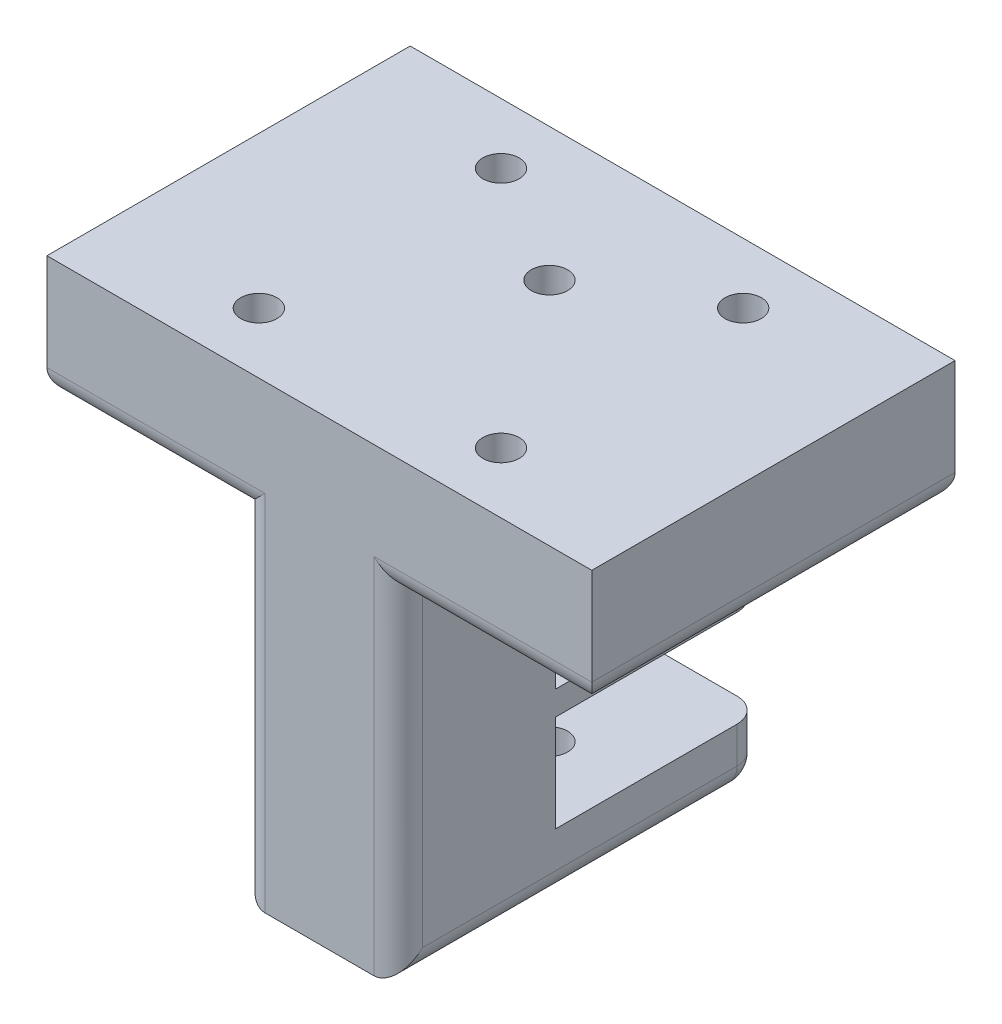
SolidWorks part; units mm, degrees
ref_plane "Front Plane" through (0, 0, 0) normal (0, 0, 1) x (1, 0, 0)
ref_plane "Top Plane" through (0, 0, 0) normal (0, 1, 0) x (1, 0, 0)
ref_plane "Right Plane" through (0, 0, 0) normal (1, 0, 0) x (0, 0, -1)
sketch "Sketch1" plane through (0, 0, 0) normal (0, 1, 0) x (1, 0, 0)
  line L1 (-20.4957, 14.8137) -> (24.5043, 14.8137)
  line L2 (-20.4957, 14.8137) -> (-20.4957, -15.1863)
  line L3 (-20.4957, -15.1863) -> (24.5043, -15.1863)
  line L4 (24.5043, 14.8137) -> (24.5043, -15.1863)
  line L5 (-20.4957, 14.8137) -> (24.5043, -15.1863) construction
  line L6 (-20.4957, -15.1863) -> (24.5043, 14.8137) construction
  line L11 (-7.9957, 9.8137) -> (12.0043, 9.8137) construction
  line L12 (-7.9957, 9.8137) -> (-7.9957, -10.1863) construction
  line L13 (-7.9957, -10.1863) -> (12.0043, -10.1863) construction
  line L14 (12.0043, 9.8137) -> (12.0043, -10.1863) construction
  line L15 (-7.9957, 9.8137) -> (12.0043, -10.1863) construction
  line L16 (-7.9957, -10.1863) -> (12.0043, 9.8137) construction
  circle A0 centre (-7.9957, 9.8137) radius 1.5
  circle A1 centre (12.0043, 9.8137) radius 1.5
  circle A2 centre (12.0043, -10.1863) radius 1.5
  circle A3 centre (-7.9957, -10.1863) radius 1.5
  point P0 (2.0043, -0.1863)
  point P7 (12.0043, 9.8137)
  point P9 (12.2604, -8.796)
  point P17 (0, 0)
  point P18 (0, 0)
  point P19 (0, 0)
  point P20 (0, 0)
  point P21 (0, 0)
  point P22 (-9.0809, -8.1131)
  dimension "D1" = 3
  dimension "D2" = 45
  dimension "D3" = 30
  dimension "D4" = 20
  dimension "D5" = 20
extrude "Boss-Extrude1" add sketch "Sketch1" against normal blind 10 contours L4 L1 L2 L3 A3 A2 A1 A0 region at (2.0043, 0, 0.1863)
sketch "Sketch5" plane through (0, -10, 0) normal (0, -1, 0) x (1, 0, 0)
  line L0 (-20.4957, 15.1863) -> (24.5043, 15.1863) construction
  line L1 (-4.4957, 15.1863) -> (8.5043, 15.1863)
  line L2 (-4.4957, 15.1863) -> (-4.4957, -14.8137)
  line L3 (-4.4957, -14.8137) -> (8.5043, -14.8137)
  line L4 (8.5043, 15.1863) -> (8.5043, -14.8137)
  line L5 (-20.4957, -14.8137) -> (24.5043, -14.8137) construction
  line L6 (-20.4957, -14.8137) -> (-20.4957, 15.1863) construction
  line L7 (-20.4957, 15.1863) -> (24.5043, 15.1863) construction
  line L8 (-20.4957, 15.1863) -> (-20.4957, -14.8137) construction
  line L9 (-20.4957, -14.8137) -> (24.5043, -14.8137) construction
  line L10 (24.5043, 15.1863) -> (24.5043, -14.8137) construction
  line L11 (-20.4957, 15.1863) -> (24.5043, -14.8137) construction
  line L12 (-20.4957, -14.8137) -> (24.5043, 15.1863) construction
  line L13 (2.0043, -999.8137) -> (2.0043, 49000.1863) construction
  point P8 (2.0043, 0.1863)
  dimension "D1" = 13
extrude "Boss-Extrude2" add sketch "Sketch5" along normal blind 28
sketch "Sketch6" plane through (0, -38, 0) normal (0, -1, 0) x (1, 0, 0)
  line L0 (8.5043, -14.8137) -> (8.5043, 15.1863) construction
  line L1 (-4.4957, 15.1863) -> (8.5043, 15.1863)
  line L2 (-4.4957, 15.1863) -> (-4.4957, 5.1863)
  line L3 (-4.4957, 5.1863) -> (8.5043, 5.1863)
  line L4 (8.5043, 15.1863) -> (8.5043, 5.1863)
  line L5 (2.0043, 5.1863) -> (2.0043, 15.1863) construction
  line L6 (-4.4957, 10.1863) -> (8.5043, 10.1863) construction
  point P232 (2.0043, 10.1863)
  dimension "D1" = 10
sketch "Sketch7" plane through (0, 0, -14.8137) normal (0, 0, -1) x (-1, 0, 0)
  line L0 (-8.5043, -38) -> (-8.5043, -10) construction
  line L1 (-8.5043, -33) -> (4.4957, -33)
  line L2 (-8.5043, -33) -> (-8.5043, -25)
  line L3 (-8.5043, -25) -> (4.4957, -25)
  line L4 (4.4957, -33) -> (4.4957, -25)
  line L5 (-2.0043, -25) -> (-2.0043, -33) construction
  line L6 (-8.5043, -29) -> (4.4957, -29) construction
  line L7 (4.4957, -38) -> (4.4957, -10) construction
  line L8 (20.4957, -10) -> (4.4957, -10) construction
  line L9 (-8.5043, -15) -> (4.4957, -15)
  line L10 (-8.5043, -15) -> (-8.5043, -23)
  line L11 (-8.5043, -23) -> (4.4957, -23)
  line L12 (4.4957, -15) -> (4.4957, -23)
  line L13 (-2.0043, -23) -> (-2.0043, -15) construction
  line L14 (-8.5043, -19) -> (4.4957, -19) construction
  line L15 (4.4957, -38) -> (-8.5043, -38) construction
  point P12 (0, 0)
  point P108 (-2.0043, -19)
  point P256 (-2.0043, -29)
  dimension "D1" = 5
  dimension "D2" = 5
  dimension "D3" = 8
extrude "Cut-Extrude1" cut sketch "Sketch7" against normal blind 17
sketch "Sketch8" plane through (0, -38, 0) normal (0, -1, 0) x (1, 0, 0)
  line L0 (-4.4957, 15.1863) -> (8.5043, -14.8137) construction
  line L1 (8.5043, 15.1863) -> (-4.4957, -14.8137) construction
  line L2 (2.0043, -995.0009) -> (2.0043, 49004.9991) construction
  line L3 (8.5043, 15.1863) -> (-4.4957, 15.1863) construction
  circle A0 centre (2.0043, -3.8137) radius 1.5
  point P11 (1.0698, -5.374)
  point P13 (2.0043, 0.1863)
  point P14 (2.0043, -1.3614)
  point P15 (2.0043, -1.5188)
  point P16 (2.0043, -3.2713)
  dimension "D1" = 3
  dimension "D2" = 19
extrude "Cut-Extrude2" cut sketch "Sketch8" against normal through all
fillet "Fillet1" radius 2 17 edges at (8.5043, -38, 0.1863) (-4.4957, -38, 0.1863) (-12.4957, -10, 15.1863) (16.5043, -10, 15.1863) (-20.4957, -10, 0.1863) (24.5043, -10, 0.1863) (-12.4957, -10, -14.8137) (16.5043, -10, -14.8137) (8.5043, -12.5, -14.8137) (8.5043, -24, -14.8137) (8.5043, -35.5, -14.8137) (-4.4957, -12.5, -14.8137) (-4.4957, -24, -14.8137) (-4.4957, -35.5, -14.8137) (8.5043, -24, 15.1863) (-4.4957, -24, 15.1863) (2.0043, -38, -14.8137)
